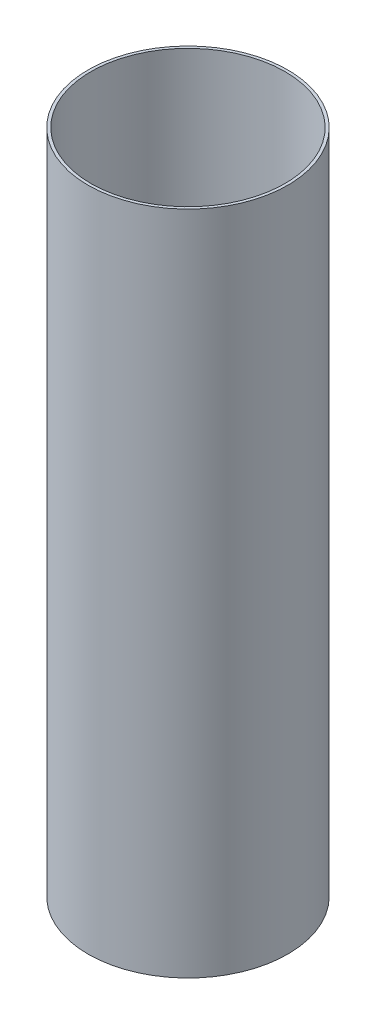
SolidWorks part; units mm, degrees
ref_plane "Спереди" through (0, 0, 0) normal (0, 0, 1) x (1, 0, 0)
ref_plane "Сверху" through (0, 0, 0) normal (0, 1, 0) x (1, 0, 0)
ref_plane "Справа" through (0, 0, 0) normal (1, 0, 0) x (0, 0, -1)
other "Configuration Table"
sketch "Эскиз1" plane through (0, 0, 0) normal (0, 1, 0) x (1, 0, 0)
  circle A0 centre (0, 0) radius 52.5
  circle A1 centre (0, 0) radius 51
  dimension "D1" = 105
  dimension "D2" = 102
extrude "Бобышка-Вытянуть1" add sketch "Эскиз1" along normal blind 350
